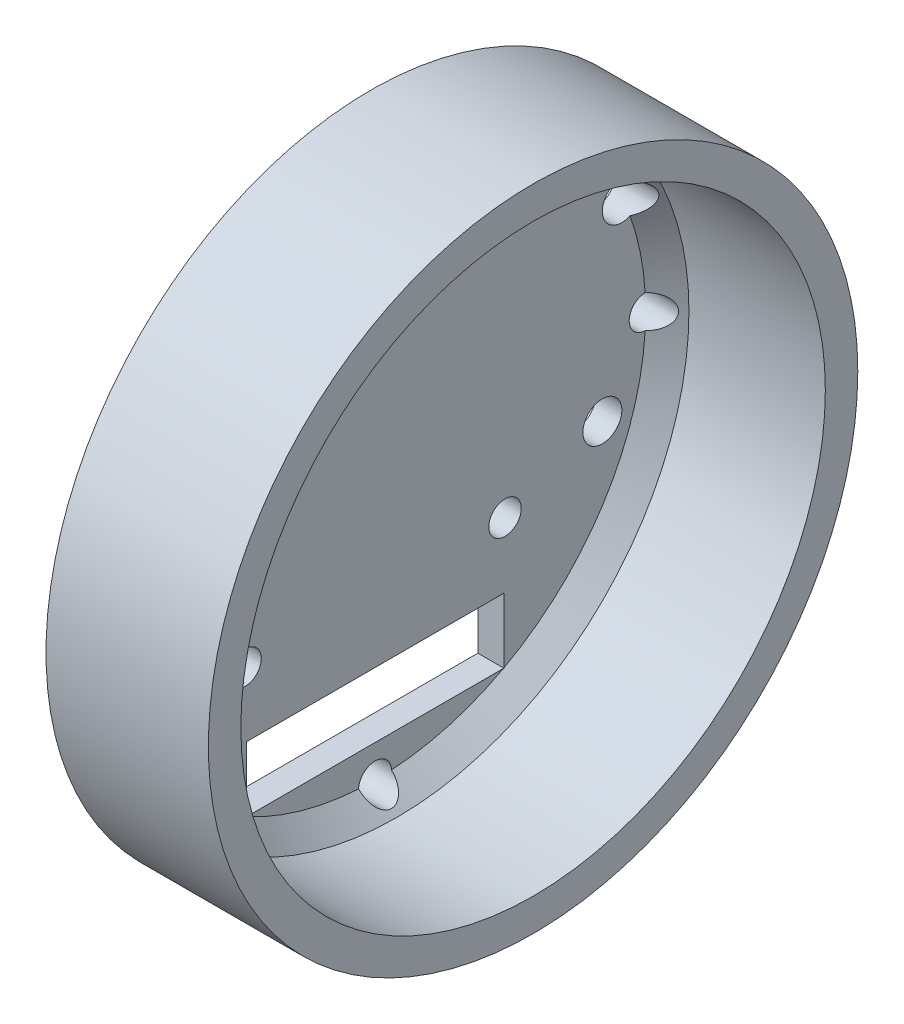
SolidWorks part; units mm, degrees
material "ABS"
ref_plane "Front Plane" through (0, 0, 0) normal (1, 0, 0) x (0, 1, 0)
ref_plane "Top Plane" through (0, 0, 0) normal (0, 0, 1) x (0, 1, 0)
ref_plane "Right Plane" through (0, 0, 0) normal (0, 1, 0) x (-1, 0, 0)
sketch "Sketch1" plane through (0, 0, 0) normal (1, 0, 0) x (0, 1, 0)
  circle A0 centre (0, 0) radius 34.29
  dimension "D1" = 68.58
extrude "Boss-Extrude1" add sketch "Sketch1" along normal blind 2.54
sketch "Sketch2" plane through (2.54, 0, 0) normal (1, 0, 0) x (0, 1, 0)
  circle A0 centre (0, 0) radius 38.1
  dimension "D1" = 76.2
extrude "Boss-Extrude2" add sketch "Sketch2" along normal blind 0.508
sketch "Sketch3" plane through (3.048, 0, 0) normal (1, 0, 0) x (0, 1, 0)
  circle A1 centre (0, 0) radius 38.1
  circle A2 centre (0, 0) radius 34.29
  dimension "D1" = 76.2
  dimension "D2" = 68.58
extrude "Boss-Extrude3" add sketch "Sketch3" along normal blind 18.542
sketch "Sketch5" plane through (3.048, 0, 0) normal (1, 0, 0) x (0, 1, 0)
  circle A0 centre (17.79, 15.25) radius 1.905
  circle A4 centre (17.79, -15.25) radius 1.905
  circle A5 centre (-12.71, -15.25) radius 1.905
  circle A6 centre (-12.71, 15.25) radius 1.905
  point P0 (-13.98, 15.25)
  point P11 (2.54, 0)
  dimension "D1" = 3.81
  dimension "D2" = 17.79
  dimension "D3" = 15.25
  dimension "D4" = 4
  dimension "D5" = 2.54
extrude "Cut-Extrude1" cut sketch "Sketch5" against normal through all
sketch "Sketch6" plane through (3.048, 0, 0) normal (1, 0, 0) x (0, 1, 0)
  circle A0 centre (28.956, 12.7) radius 2.286
  circle A5 centre (12.7, -28.956) radius 2.286
  circle A7 centre (-12.7, 28.956) radius 2.286
  circle A8 centre (-28.956, -12.7) radius 2.286 [skipped]
  point P12 (0, 0)
  dimension "D2" = 4.572
  dimension "D1" = 12.7
  dimension "D4" = 4
  dimension "D3" = 28.956
extrude "Cut-Extrude10" cut sketch "Sketch6" against normal through all
chamfer "Chamfer2" distance 2.54 angle 45 1 edges at (3.048, 0, -34.29)
sketch "Sketch7" plane through (3.048, 0, 0) normal (1, 0, 0) x (0, 1, 0)
  line L1 (7.9351, 20.32) -> (20.6351, 20.32)
  line L2 (7.9351, 20.32) -> (7.9351, 24.13)
  line L3 (7.9351, 24.13) -> (20.6351, 24.13)
  line L4 (20.6351, 20.32) -> (20.6351, 24.13)
  arc A0 (28.0829, 14.8127) -> (-10.6267, 29.9188) centre (0, 0) ccw construction
  point P4 (20.3658, 24.3577)
  dimension "D1" = 3.81
  dimension "D2" = 12.7
  dimension "D3" = 20.32
extrude "Cut-Extrude11" cut sketch "Sketch7" against normal through all
chamfer "Chamfer3" distance 1.905 angle 45 1 edges at (2.54, 0, -34.29)
sketch "Sketch8" plane through (3.048, 0, 0) normal (1, 0, 0) x (0, 1, 0)
  circle A0 centre (0, -31.75) radius 1.9304
  circle A1 centre (-31.75, 0) radius 1.9304
  circle A2 centre (0, 31.75) radius 1.9304
  circle A3 centre (31.75, 0) radius 1.9304
  point P9 (0, 0)
  dimension "D2" = 3.8608
  dimension "D1" = 31.75
  dimension "D3" = 4
extrude "Cut-Extrude12" cut sketch "Sketch8" against normal through all both and the other way through all
sketch "Sketch9" plane through (3.048, 0, 0) normal (1, 0, 0) x (0, 1, 0)
  line L1 (-27.94, -15.113) -> (-20.32, -15.113)
  line L2 (-27.94, -15.113) -> (-27.94, 15.113)
  line L3 (-27.94, 15.113) -> (-20.32, 15.113)
  line L4 (-20.32, -15.113) -> (-20.32, 15.113)
  line L5 (-27.94, -15.113) -> (-20.32, 15.113) construction
  line L6 (-27.94, 15.113) -> (-20.32, -15.113) construction
  arc A0 (-31.6913, -1.9295) -> (-31.6913, 1.9295) centre (-31.75, 0) ccw construction
  point P0 (-24.13, 0)
  point P5 (0, 0)
  dimension "D3" = 3.81
  dimension "D1" = 7.62
  dimension "D2" = 30.226
extrude "Cut-Extrude13" cut sketch "Sketch9" against normal through all both and the other way through all
sketch "Sketch10" plane through (3.048, 0, 0) normal (1, 0, 0) x (0, 0, -1)
  circle A0 centre (26.67, -8.636) radius 2.286
  arc A1 (31.6913, 1.9295) -> (31.6913, -1.9295) centre (31.75, 0) ccw construction
  point P7 (30.4623, 5.2937)
  dimension "D1" = 4.572
  dimension "D2" = 8.636
  dimension "D3" = 5.08
extrude "Cut-Extrude14" cut sketch "Sketch10" against normal through all both and the other way through all
